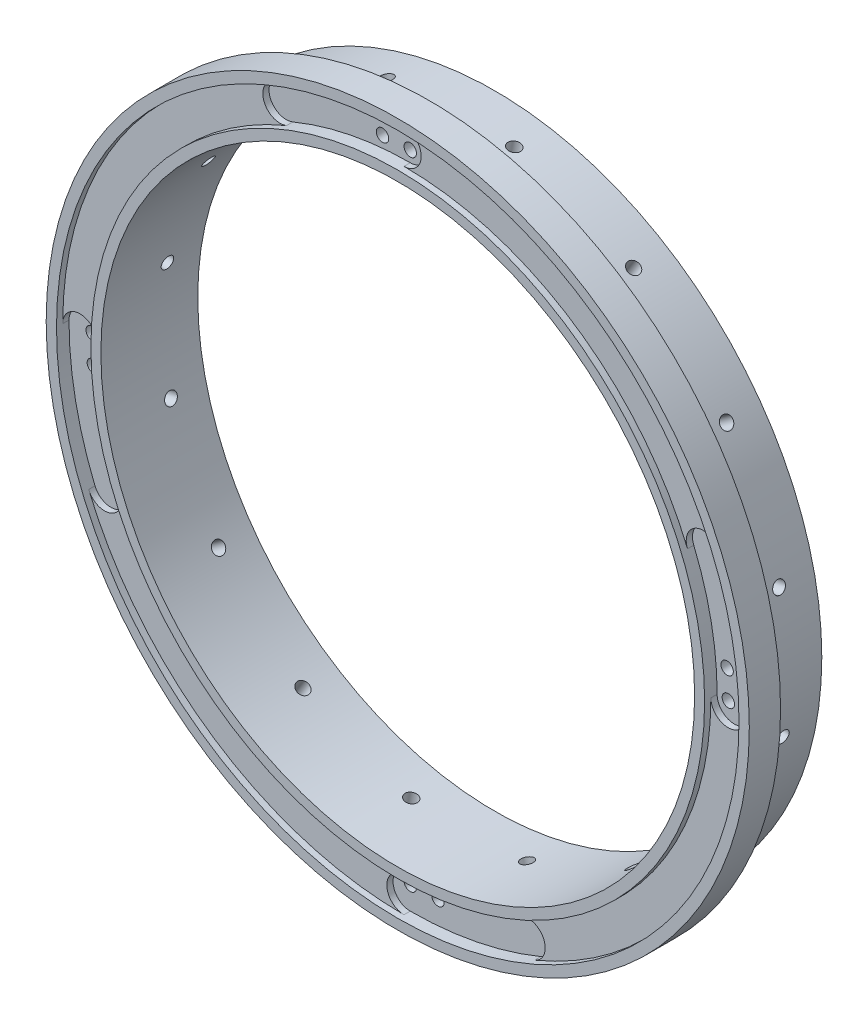
SolidWorks part; units mm, degrees
material "6061-T6 (SS)"
ref_plane "Front Plane" through (0, 0, 0) normal (0, 0, 1) x (1, 0, 0)
ref_plane "Top Plane" through (0, 0, 0) normal (0, 1, 0) x (1, 0, 0)
ref_plane "Right Plane" through (0, 0, 0) normal (1, 0, 0) x (0, 0, -1)
sketch "Sketch1" plane through (0, 0, 0) normal (0, 0, 1) x (1, 0, 0)
  circle A0 centre (0, 0) radius 71.4375
  dimension "D1" = 142.875
extrude "Extrude1" add sketch "Sketch1" along normal blind 19.685
sketch "Sketch2" plane through (0, 0, 19.685) normal (0, 0, 1) x (1, 0, 0)
  circle A0 centre (0, 0) radius 60.325
  dimension "D1" = 120.65
extrude "Extrude2" cut sketch "Sketch2" against normal through all
sketch "Sketch3" plane through (0, 0, 0) normal (0, 0, -1) x (-1, 0, 0)
  circle A0 centre (0, 0) radius 66.4845
  dimension "D1" = 132.969
extrude "Extrude3" cut sketch "Sketch3" against normal blind 13.335 flip side to cut
sketch "Sketch4" plane through (0, 0, 19.685) normal (0, 0, 1) x (1, 0, 0)
  circle A0 centre (0, 0) radius 62.357
  circle A1 centre (0, 0) radius 69.342
  dimension "D1" = 124.714
  dimension "D2" = 138.684
extrude "Extrude4" cut sketch "Sketch4" against normal blind 1.27
sketch "Sketch5" plane through (0, 0, 18.415) normal (0, 0, 1) x (1, 0, 0)
  line L0 (0, 0) -> (0, 69.342) construction
  line L1 (0, 69.342) -> (0, -69.342) construction
  line L2 (0, 0) -> (62.357, 0) construction
  line L3 (0, -69.342) -> (0, 0) construction
  line L4 (0, 0) -> (69.342, 0) construction
  line L5 (69.342, 0) -> (-69.342, 0) construction
  circle A0 centre (0, 0) radius 62.357 construction
  circle A2 centre (0, 0) radius 69.342 construction
sketch "Sketch7" plane through (0, 0, 18.415) normal (0, 0, 1) x (1, 0, 0)
  line L0 (69.342, 0) -> (-69.342, 0) construction
  line L1 (0, 0) -> (0, 69.342) construction
  line L2 (0, 69.342) -> (0, 62.357) construction
  line L3 (-26.536, 64.0637) -> (-23.863, 57.6104) construction
  arc A0 (0, 69.342) -> (-26.536, 64.0637) centre (0, 0) ccw
  arc A1 (0, 62.357) -> (-23.863, 57.6104) centre (0, 0) ccw
  circle A2 centre (0, 0) radius 62.357 construction
  arc A3 (-26.536, 64.0637) -> (-23.863, 57.6104) centre (-25.1995, 60.837) ccw
  arc A4 (0, 69.342) -> (0, 62.357) centre (0, 65.8495) cw
extrude "Extrude6" cut sketch "Sketch7" against normal blind 1.27 and the other way through all
pattern_circular "CirPattern1" count 4 over 360 about axis through (0, 0, 0) along (0, 0, 1) of "Extrude6"
sketch "Sketch8" plane through (0, 0, 17.145) normal (0, 0, 1) x (1, 0, 0)
  circle A0 centre (0, 0) radius 64.6327
  arc A1 (0, 64.6327) -> (-5.6331, 64.3868) centre (0, 0) ccw
hole_wizard "#39 (0.0995) Diameter Hole1" positions "3DSketch1" profile "Sketch9" hole size "#39" standard "Ansi Inch" end condition through all
sketch3d "3DSketch1"
  point P0 (0, 64.6327, 17.145)
  point P3 (-5.6331, 64.3868, 17.145)
sketch "Sketch9" plane through (0, 64.6327, 17.145) normal (1, 0, 0) x (0, -1, 0)
  line L0 (0, 0) -> (0, 17.145)
  line L1 (0, 17.145) -> (1.2636, 17.145)
  line L2 (1.2636, 17.145) -> (1.2636, 0)
  line L5 (1.2636, 0) -> (0, 0)
  line L11 (0, -6.35) -> (0, 107.95) construction
  dimension "Thru Hole Dia." = 2.5273
  dimension "Thru Hole Depth" = 17.145
pattern_circular "CirPattern2" count 4 over 360 about axis through (0, 0, 0) along (0, 0, 1) of "#39 (0.0995) Diameter Hole1"
ref_plane "Plane1" through (0, 0, 6.985) normal (0, 0, -1) x (-1, 0, 0)
sketch "Sketch15" plane through (0, 0, 6.985) normal (0, 0, -1) x (-1, 0, 0)
  line L0 (0, 0) -> (-66.4845, 0) construction
  line L1 (-2.314, 46.2834) -> (-2.314, 63.5529) construction
  line L2 (0, 0) -> (-69.342, 0) construction
  line L3 (0, 0) -> (-64.7805, 14.9558) construction
  circle A0 centre (0, 0) radius 66.4845 construction
ref_plane "Plane3" through (64.7805, 14.9558, 6.985) normal (0.9744, 0.225, 0) x (0, 0, -1)
hole_wizard "#39 (0.0995) Diameter Hole5" positions "Sketch17" profile "Sketch16" hole size "#39" standard "Ansi Inch"
sketch "Sketch17" plane through (64.7805, 14.9558, 6.985) normal (0.9744, 0.225, 0) x (0, 0, -1)
  point P1 (0, 0)
sketch "Sketch16" plane through (64.7805, 14.9558, 6.985) normal (0, 0, 1) x (-0.225, 0.9744, 0)
  line L0 (0, 0) -> (0, 13.4593)
  line L1 (0, 13.4593) -> (1.2636, 12.7)
  line L2 (1.2636, 12.7) -> (1.2636, 0)
  line L5 (1.2636, 0) -> (0, 0)
  line L10 (0, 13.4593) -> (-1.2636, 12.7) construction
  line L11 (0, -6.35) -> (0, 107.95) construction
  dimension "Hole Dia." = 2.5273
  dimension "Hole Depth" = 12.7
  dimension "Drill Angle" = 118
pattern_circular "CirPattern4" count 16 over 360 about axis through (0, 0, 0) along (0, 0, 1) of "#39 (0.0995) Diameter Hole5" reverse direction yes
